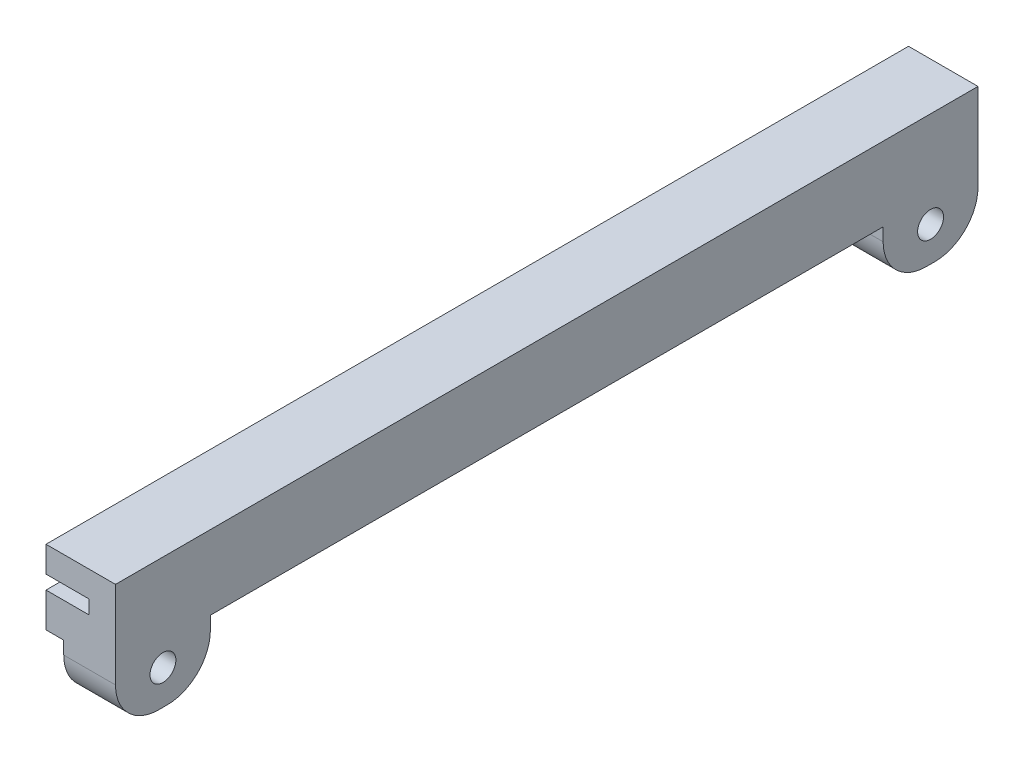
SolidWorks part; units mm, degrees
ref_plane "Front Plane" through (0, 0, 0) normal (0, 0, 1) x (1, 0, 0)
ref_plane "Top Plane" through (0, 0, 0) normal (0, 1, 0) x (1, 0, 0)
ref_plane "Right Plane" through (0, 0, 0) normal (1, 0, 0) x (0, 0, -1)
sketch "Sketch1" plane through (0, 0, 0) normal (0, 1, 0) x (1, 0, 0)
  line L1 (-3.5288, -50) -> (3.5288, -50)
  line L2 (-3.5288, -50) -> (-3.5288, 50)
  line L3 (-3.5288, 50) -> (3.5288, 50)
  line L4 (3.5288, -50) -> (3.5288, 50)
  line L5 (-3.5288, -50) -> (3.5288, 50) construction
  line L6 (-3.5288, 50) -> (3.5288, -50) construction
  point P0 (0, 0)
  dimension "D1" = 100
  dimension "D2" = 7.0575
extrude "Boss-Extrude2" add sketch "Sketch1" along normal blind 7.6
sketch "Sketch4" plane through (0, 7.6, 0) normal (0, 1, 0) x (1, 0, 0)
  line L0 (3.5288, -50) -> (3.5288, 50) construction
  line L1 (3.5288, 43.218) -> (-1.4713, 43.218)
  line L2 (3.5288, 43.218) -> (3.5288, -50)
  line L3 (3.5288, -50) -> (-1.4713, -50)
  line L4 (-1.4713, 43.218) -> (-1.4713, -50)
  line L6 (3.5288, 50) -> (-3.5288, 50) construction
  line L7 (-3.5288, 50) -> (-3.5288, -50) construction
  dimension "D1" = 6.782
  dimension "D2" = 2.0575
extrude "Cut-Extrude1" cut sketch "Sketch4" against normal blind 4.6
sketch "Sketch6" plane through (0, 7.6, 0) normal (0, 1, 0) x (1, 0, 0)
  line L1 (3.5288, 43.218) -> (-1.4713, 43.218)
  line L2 (3.5288, 43.218) -> (3.5288, -50)
  line L3 (3.5288, -50) -> (-1.4713, -50)
  line L4 (-1.4713, 43.218) -> (-1.4713, -50)
extrude "Boss-Extrude3" add sketch "Sketch6" against normal blind 3
sketch "Sketch8" plane through (0, 0, 0) normal (0, -1, 0) x (1, 0, 0)
  line L1 (-3.5288, 50) -> (3.5288, 50)
  line L2 (-3.5288, 50) -> (-3.5288, -50)
  line L3 (-3.5288, -50) -> (3.5288, -50)
  line L4 (3.5288, 50) -> (3.5288, -50)
extrude "Boss-Extrude4" add sketch "Sketch8" along normal blind 1
sketch "Sketch9" plane through (0, -1, 0) normal (0, -1, 0) x (1, 0, 0)
  line L1 (-3.5288, 50) -> (1.4712, 50)
  line L2 (-3.5288, 50) -> (-3.5288, 39)
  line L3 (-3.5288, 39) -> (1.4712, 39)
  line L4 (1.4712, 50) -> (1.4712, 39)
  line L5 (-3.5288, -50) -> (1.4712, -50)
  line L6 (-3.5288, -50) -> (-3.5288, -39)
  line L7 (-3.5288, -39) -> (1.4712, -39)
  line L8 (1.4712, -50) -> (1.4712, -39)
  point P10 (1.4712, -44.5)
  dimension "D1" = 11
  dimension "D2" = 11
  dimension "D3" = 5
  dimension "D4" = 5
extrude "Boss-Extrude5" add sketch "Sketch9" along normal blind 6.5 contours L2 L1 L4 L3 | L6 L5 L8 L7
sketch "Sketch10" plane through (1.4713, 0, 0) normal (1, 0, 0) x (0, 0, -1)
  line L0 (-50, -7.5) -> (-50, -1) construction
  line L1 (-46.0877, -0.75) -> (-47.6754, -3.5)
  line L2 (-47.6754, -3.5) -> (-46.0877, -6.25)
  line L3 (-46.0877, -6.25) -> (-42.9123, -6.25)
  line L4 (-42.9123, -6.25) -> (-41.3246, -3.5)
  line L5 (-41.3246, -3.5) -> (-42.9123, -0.75)
  line L6 (-42.9123, -0.75) -> (-46.0877, -0.75)
  line L7 (-50, -7.5) -> (-39, -7.5) construction
  line L8 (39, -7.5) -> (39, -1) construction
  line L9 (47.6754, -3.5) -> (46.0877, -0.75)
  line L10 (46.0877, -0.75) -> (42.9123, -0.75)
  line L11 (42.9123, -0.75) -> (41.3246, -3.5)
  line L12 (41.3246, -3.5) -> (42.9123, -6.25)
  line L13 (42.9123, -6.25) -> (46.0877, -6.25)
  line L14 (46.0877, -6.25) -> (47.6754, -3.5)
  line L15 (50, -7.5) -> (39, -7.5) construction
  circle A0 centre (-44.5, -3.5) radius 2.75 construction
  circle A1 centre (44.5, -3.5) radius 2.75 construction
  dimension "D1" = 5.5
  dimension "D2" = 5.5
  dimension "D3" = 1.25
  dimension "D4" = 5.5
  dimension "D5" = 1.25
  dimension "D6" = 5.5
extrude "Cut-Extrude2" cut sketch "Sketch10" against normal blind 2.4
sketch "Sketch11" plane through (-0.9287, 0, 0) normal (1, 0, 0) x (0, 0, -1)
  line L2 (-50, -7.5) -> (-39, -7.5) construction
  line L3 (-50, -7.5) -> (-50, -1) construction
  line L4 (39, -7.5) -> (39, -1) construction
  line L5 (50, -7.5) -> (39, -7.5) construction
  circle A0 centre (-44.5, -3.5) radius 1.5
  circle A1 centre (44.5, -3.5) radius 1.5
  dimension "D3" = 3
  dimension "D4" = 3
  dimension "D1" = 4
  dimension "D2" = 5.5
  dimension "D5" = 5.5
  dimension "D6" = 4
extrude "Cut-Extrude3" cut sketch "Sketch11" against normal through all contours A0 | A1
fillet "Fillet2" radius 5 4 edges at (-1.0288, -7.5, -50) (-1.0288, -7.5, -39) (-1.0288, -7.5, 39) (-1.0288, -7.5, 50)
sketch "Sketch13" plane through (-3.5288, 0, 0) normal (-1, 0, 0) x (0, 0, 1)
  line L0 (-45, -7.5) -> (-44, -7.5) construction
  line L1 (-39, -2.5) -> (-39, -1) construction
  line L2 (39, -1) -> (-39, -1) construction
  line L3 (39, -2.5) -> (39, -1) construction
  line L4 (45, -7.5) -> (44, -7.5) construction
  line L5 (50, 7.6) -> (50, -2.5) construction
  line L6 (-50, 7.6) -> (50, 7.6) construction
  line L7 (-50, 7.6) -> (-50, -2.5) construction
  line L8 (-45, -7.5) -> (-44, -7.5)
  line L9 (-39, -2.5) -> (-39, -1)
  line L10 (39, -1) -> (-39, -1)
  line L11 (39, -2.5) -> (39, -1)
  line L12 (45, -7.5) -> (44, -7.5)
  line L13 (50, 7.6) -> (50, -2.5)
  line L14 (-50, 7.6) -> (50, 7.6)
  line L15 (-50, 7.6) -> (-50, -2.5)
  circle A0 centre (-44.5, -3.5) radius 1.5 construction
  arc A1 (-50, -2.5) -> (-45, -7.5) centre (-45, -2.5) ccw construction
  arc A2 (-44, -7.5) -> (-39, -2.5) centre (-44, -2.5) ccw construction
  arc A3 (39, -2.5) -> (44, -7.5) centre (44, -2.5) ccw construction
  circle A4 centre (44.5, -3.5) radius 1.5 construction
  arc A5 (45, -7.5) -> (50, -2.5) centre (45, -2.5) ccw construction
  circle A6 centre (-44.5, -3.5) radius 1.5
  arc A7 (-50, -2.5) -> (-45, -7.5) centre (-45, -2.5) ccw
  arc A8 (-44, -7.5) -> (-39, -2.5) centre (-44, -2.5) ccw
  arc A9 (39, -2.5) -> (44, -7.5) centre (44, -2.5) ccw
  circle A10 centre (44.5, -3.5) radius 1.5
  arc A11 (45, -7.5) -> (50, -2.5) centre (45, -2.5) ccw
extrude "Boss-Extrude6" add sketch "Sketch13" along normal blind 1
mirror "Mirror2" about plane through (3.5288, 7.6, 50) normal (-1, 0, 0) of bodies 109
delete or keep bodies "Body-Delete/Keep 1" type delete bodies bodies 109
